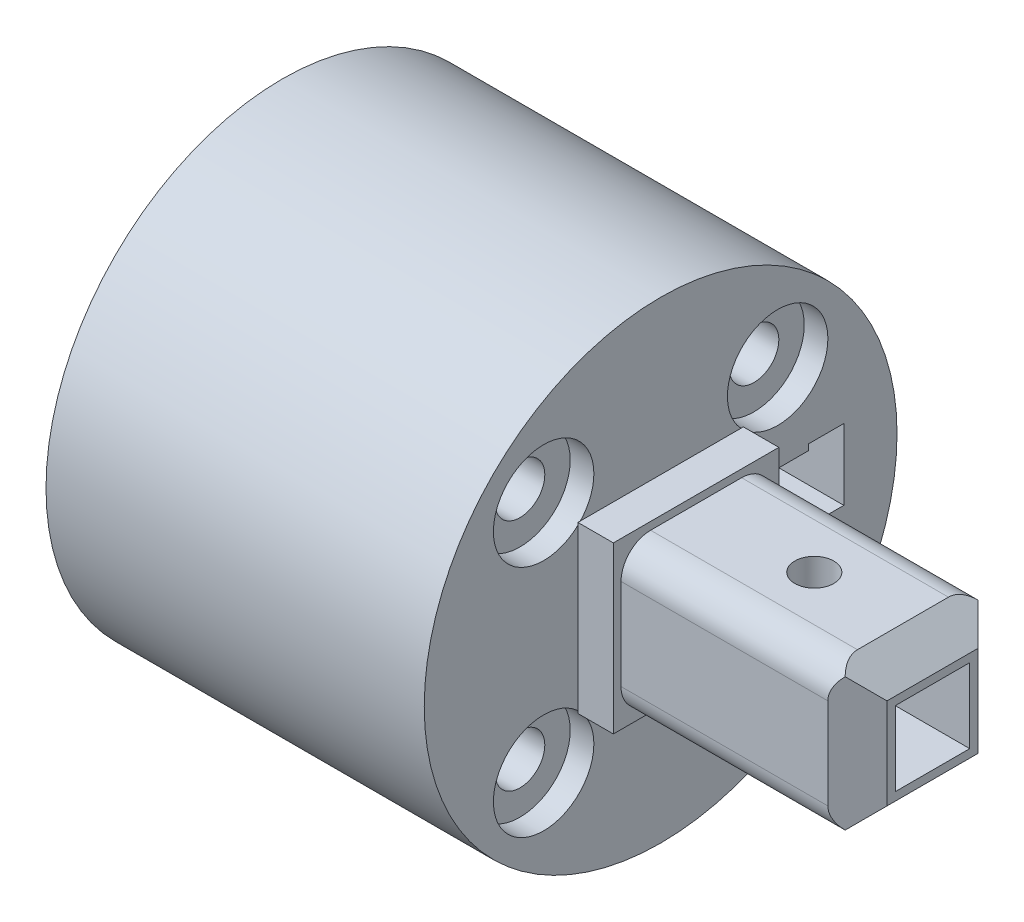
SolidWorks part; units mm, degrees
ref_plane "前视基准面" through (0, 0, 0) normal (0, 0, 1) x (1, 0, 0)
ref_plane "上视基准面" through (0, 0, 0) normal (0, 1, 0) x (1, 0, 0)
ref_plane "右视基准面" through (0, 0, 0) normal (1, 0, 0) x (0, 0, -1)
sketch "草图1" plane through (0, 0, 0) normal (1, 0, 0) x (0, 0, -1)
  circle A0 centre (0, 0) radius 20
  dimension "D1" = 40
extrude "凸台-拉伸1" add sketch "草图1" along normal blind 5
sketch "草图2" plane through (5, 0, 0) normal (1, 0, 0) x (0, 0, -1)
  line L1 (-3.15, -3.15) -> (3.15, -3.15)
  line L2 (-3.15, -3.15) -> (-3.15, 3.15)
  line L3 (-3.15, 3.15) -> (3.15, 3.15)
  line L4 (3.15, -3.15) -> (3.15, 3.15)
  line L5 (-3.15, -3.15) -> (3.15, 3.15) construction
  line L6 (-3.15, 3.15) -> (3.15, -3.15) construction
  point P0 (0, 0)
  dimension "D1" = 6.3
  dimension "D2" = 6.3
extrude "切除-拉伸1" cut sketch "草图2" against normal blind 5
sketch "草图4" plane through (0, 0, 0) normal (-1, 0, 0) x (0, 0, 1)
  circle A0 centre (0, 0) radius 20
  circle A1 centre (0, 0) radius 10
  dimension "D1" = 20
extrude "凸台-拉伸2" add sketch "草图4" along normal blind 7
sketch "草图3" plane through (0, 0, 0) normal (-1, 0, 0) x (0, 0, 1)
  line L0 (0, 0) -> (20, 0) construction
  line L1 (0, 0) -> (21.8171, -21.8171) construction
  circle A0 centre (0, 0) radius 14 construction
  circle A3 centre (9.8995, -9.8995) radius 2.1
  circle A4 centre (0, 0) radius 14 construction
  circle A5 centre (-9.8995, -9.8995) radius 2.1
  circle A6 centre (0, 0) radius 14 construction
  circle A7 centre (-9.8995, 9.8995) radius 2.1
  circle A8 centre (0, 0) radius 14 construction
  circle A9 centre (9.8995, 9.8995) radius 2.1
  point P22 (0, 0)
  dimension "D1" = 28
  dimension "D2" = 4.2
  dimension "D3" = 45
  dimension "D4" = 4
extrude "切除-拉伸2" cut sketch "草图3" against normal blind 20 and the other way blind 20
sketch "草图5" plane through (5, 0, 0) normal (1, 0, 0) x (0, 0, -1)
  line L1 (15.5, -3) -> (12.5, -3)
  line L2 (15.5, -3) -> (15.5, 3)
  line L3 (15.5, 3) -> (12.5, 3)
  line L4 (12.5, -3) -> (12.5, 3)
  line L5 (15.5, -3) -> (12.5, 3) construction
  line L6 (15.5, 3) -> (12.5, -3) construction
  point P0 (14, 0)
  dimension "D1" = 14
  dimension "D2" = 3
  dimension "D3" = 6
extrude "切除-拉伸3" cut sketch "草图5" against normal blind 13
chamfer "倒角1" distance 1 angle 45 4 edges at (-7, 3, -14) (-7, 0, -15.5) (-7, -3, -14) (-7, 0, -12.5)
sketch "草图6" plane through (-7, 0, 0) normal (-1, 0, 0) x (0, 0, 1)
  circle A0 centre (0, 0) radius 20
  circle A1 centre (0, 0) radius 18
  dimension "D1" = 40
  dimension "D2" = 36
extrude "凸台-拉伸3" add sketch "草图6" along normal blind 20
chamfer "倒角2" distance 1 angle 45 1 edges at (-27, 0, 18)
sketch "草图7" plane through (5, 0, 0) normal (1, 0, 0) x (0, 0, -1)
  circle A0 centre (-9.8995, 9.8995) radius 4.25
  circle A1 centre (9.8995, 9.8995) radius 4.25
  circle A2 centre (9.8995, -9.8995) radius 4.25
  circle A3 centre (-9.8995, -9.8995) radius 4.25
  point P12 (0, 0)
  dimension "D1" = 8.5
  dimension "D2" = 4
extrude "切除-拉伸4" cut sketch "草图7" against normal blind 2
sketch "草图8" plane through (5, 0, 0) normal (1, 0, 0) x (0, 0, -1)
  line L1 (7, -7) -> (-7, -7)
  line L2 (7, -7) -> (7, 7)
  line L3 (7, 7) -> (-7, 7)
  line L4 (-7, -7) -> (-7, 7)
  line L5 (7, -7) -> (-7, 7) construction
  line L6 (7, 7) -> (-7, -7) construction
  point P0 (0, 0)
  dimension "D1" = 14
  dimension "D2" = 14
extrude "凸台-拉伸4" add sketch "草图8" along normal blind 3
sketch "草图9" plane through (5, 0, 0) normal (-1, 0, 0) x (0, 0, 1)
  line L1 (-3.15, -3.15) -> (3.15, -3.15)
  line L2 (-3.15, -3.15) -> (-3.15, 3.15)
  line L3 (-3.15, 3.15) -> (3.15, 3.15)
  line L4 (3.15, -3.15) -> (3.15, 3.15)
  line L5 (-3.15, -3.15) -> (3.15, 3.15) construction
  line L6 (-3.15, 3.15) -> (3.15, -3.15) construction
  point P0 (0, 0)
  dimension "D1" = 6.3
extrude "切除-拉伸5" cut sketch "草图9" against normal blind 10
sketch "草图10" plane through (0, 0, -7) normal (0, 0, -1) x (-1, 0, 0)
  line L0 (-5, -6.7922) -> (-5, 6.7922) construction
  line L1 (-3.5, -2.5) -> (-6.5, -2.5)
  line L2 (-3.5, -2.5) -> (-3.5, 2.5)
  line L3 (-3.5, 2.5) -> (-6.5, 2.5)
  line L4 (-6.5, -2.5) -> (-6.5, 2.5)
  line L5 (-3.5, -2.5) -> (-6.5, 2.5) construction
  line L6 (-3.5, 2.5) -> (-6.5, -2.5) construction
  point P0 (-5, 0)
  dimension "D1" = 3
  dimension "D2" = 5
extrude "切除-拉伸6" cut sketch "草图10" against normal blind 5 and the other way blind 6
fillet "圆角1" radius 4 1 edges at (3.5, 0, -12.5)
fillet "圆角2" radius 2 1 edges at (6.5, 0, -3.15)
sketch "草图11" plane through (8, 0, 0) normal (1, 0, 0) x (0, 0, -1)
  line L1 (6.35, -6.35) -> (-6.35, -6.35)
  line L2 (6.35, -6.35) -> (6.35, 6.35)
  line L3 (6.35, 6.35) -> (-6.35, 6.35)
  line L4 (-6.35, -6.35) -> (-6.35, 6.35)
  line L5 (6.35, -6.35) -> (-6.35, 6.35) construction
  line L6 (6.35, 6.35) -> (-6.35, -6.35) construction
  line L8 (-3.15, -3.15) -> (3.15, -3.15)
  line L9 (-3.15, -3.15) -> (-3.15, 3.15)
  line L10 (-3.15, 3.15) -> (3.15, 3.15)
  line L11 (3.15, -3.15) -> (3.15, 3.15)
  line L12 (-3.15, -3.15) -> (3.15, 3.15) construction
  line L13 (-3.15, 3.15) -> (3.15, -3.15) construction
  point P0 (0, 0)
  point P6 (0, 0)
  dimension "D1" = 12.7
  dimension "D2" = 12.7
extrude "凸台-拉伸5" add sketch "草图11" along normal blind 20
chamfer "倒角3" distance 2.5 angle 45 4 edges at (28, 6.35, 0) (28, 0, -6.35) (28, -6.35, 0) (28, 0, 6.35)
sketch "草图12" plane through (0, -6.35, 0) normal (0, -1, 0) x (1, 0, 0)
  line L0 (8, 6.35) -> (8, -6.35) construction
  circle A0 centre (18, 0) radius 1.65
  dimension "D1" = 3.3
  dimension "D2" = 10
extrude "切除-拉伸7" cut sketch "草图12" against normal blind 20
fillet "圆角3" radius 2.5 4 edges at (16.75, -6.35, 6.35) (16.75, 6.35, 6.35) (16.75, 6.35, -6.35) (16.75, -6.35, -6.35)
